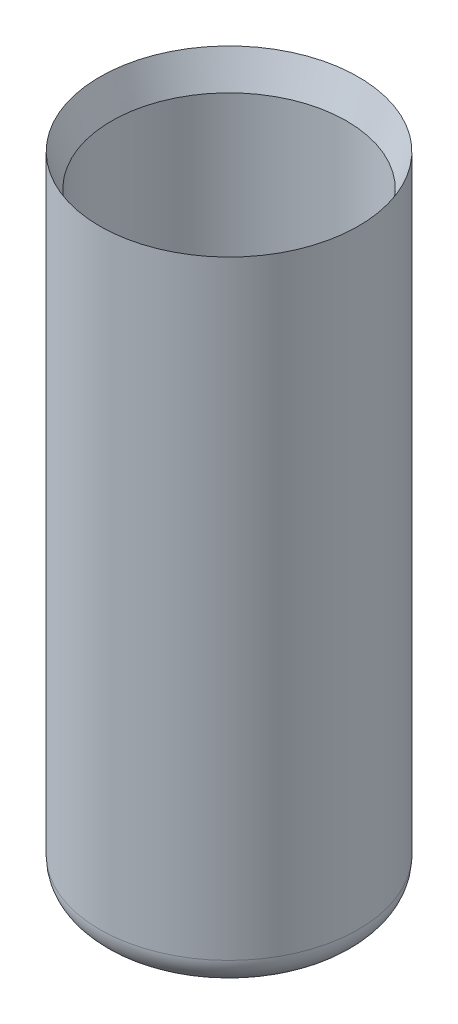
SolidWorks part; units mm, degrees
note: The reader was unsure of these and kept them because the rebuilt part matched: shared geometry of "Sketch1<3>".
ref_plane "Front Plane" through (0, 0, 0) normal (0, 0, 1) x (1, 0, 0)
ref_plane "Top Plane" through (0, 0, 0) normal (0, 1, 0) x (1, 0, 0)
ref_plane "Right Plane" through (0, 0, 0) normal (1, 0, 0) x (0, 0, -1)
sketch "Sketch1" plane through (0, 0, 0) normal (0, 1, 0) x (1, 0, 0)
  circle A0 centre (0, 0) radius 20
  circle A1 centre (0, 0) radius 22
  dimension "D2" = 40
  dimension "D1" = 2
extrude "Boss-Extrude1" add sketch "Sketch1" against normal blind 10 contours A1 A0 | A0
extrude "Boss-Extrude2" add sketch "Sketch1<3>" along normal blind 100
sketch "Sketch1<3>" plane through (0, 0, 0) normal (0, 1, 0) x (1, 0, 0) same geometry as "Sketch1"
fillet "Fillet1" radius 5 1 edges at (0, 0, 20)
fillet "Fillet2" radius 5 1 edges at (0, -10, 22)
sketch "Sketch2" plane through (0, -10, 0) normal (0, -1, 0) x (1, 0, 0)
  line L0 (-2.1651, 10.75) -> (-10.3923, -3.5)
  line L1 (-8.2272, -7.25) -> (8.2272, -7.25)
  line L2 (10.3923, -3.5) -> (2.1651, 10.75)
  line L3 (-6.2787, 3.625) -> (8.2272, -4.75) construction
  line L4 (8.2272, -4.75) -> (0, 9.5)
  line L5 (6.2787, 3.625) -> (-8.2272, -4.75) construction
  line L6 (0, 9.5) -> (-8.2272, -4.75)
  line L7 (0, -7.25) -> (0, 9.5) construction
  line L8 (-8.2272, -4.75) -> (8.2272, -4.75)
  line L9 (-2.5, 12) -> (-2.5, 0)
  line L10 (2.5, 0) -> (2.5, 12)
  arc A0 (2.1651, 10.75) -> (-2.1651, 10.75) centre (0, 9.5) ccw
  arc A1 (-10.3923, -3.5) -> (-8.2272, -7.25) centre (-8.2272, -4.75) ccw
  arc A2 (8.2272, -7.25) -> (10.3923, -3.5) centre (8.2272, -4.75) ccw
  circle A4 centre (0, 0) radius 12 construction
  circle A5 centre (0, 0) radius 17 construction
  arc A6 (0, 9.5) -> (0, 9.5) centre (0, 9.5) ccw
  arc A7 (-8.2272, -4.75) -> (-8.2272, -4.75) centre (-8.2272, -4.75) ccw
  arc A8 (8.2272, -4.75) -> (8.2272, -4.75) centre (8.2272, -4.75) ccw
  arc A9 (-2.5, 12) -> (2.5, 12) centre (0, 12) cw
  arc A10 (-2.5, 0) -> (2.5, 0) centre (0, 0) ccw
  circle A11 centre (0, -6) radius 2.5
  point P10 (0, 0)
  dimension "D1" = 2.5
  dimension "D2" = 5
  dimension "D4" = 5
  dimension "D5" = 12
  dimension "D6" = 6
  dimension "D3" = 2.5
extrude "Boss-Extrude3" add sketch "Sketch2" along normal blind 2 contours L1 A2 L2 A0 L0 A1 L8 L6 L4 | L9 A10 L10 A9 | A11
chamfer "Chamfer1" distance 2.5 angle 70 1 edges at (0, 100, 20)
equation "\"inner_diameter\" = 40mm"
equation "\"D2@Sketch1\"=\"inner_diameter\""
